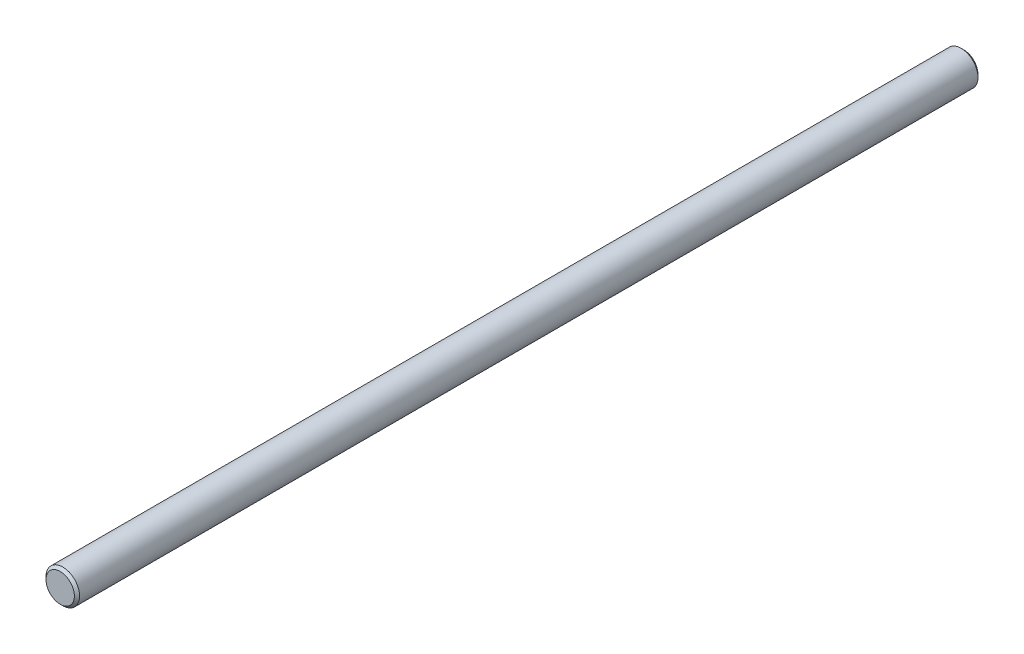
SolidWorks part; units mm, degrees
ref_plane "Front Plane" through (0, 0, 0) normal (0, 0, 1) x (1, 0, 0)
ref_plane "Top Plane" through (0, 0, 0) normal (0, 1, 0) x (1, 0, 0)
ref_plane "Right Plane" through (0, 0, 0) normal (1, 0, 0) x (0, 0, -1)
sketch "Sketch1" plane through (0, 0, 0) normal (0, 1, 0) x (1, 0, 0)
  line L1 (6.5, 350) -> (0, 350)
  line L2 (6.5, 350) -> (6.5, 0)
  line L3 (6.5, 0) -> (0, 0)
  line L4 (0, 350) -> (0, 0)
  line L5 (6.5, 350) -> (0, 0) construction
  line L6 (6.5, 0) -> (0, 350) construction
  point P0 (3.25, 175)
  dimension "D1" = 6.5
  dimension "D2" = 350
revolve "Revolve1" add sketch "Sketch1" angle 360 about L4
chamfer "Chamfer1" distance 1 angle 45 2 edges at (-6.5, 0, 0) (-6.5, 0, -350)
ref_axis "Axis1" through (0, 0, 3.117) along (0, 0, -1)
